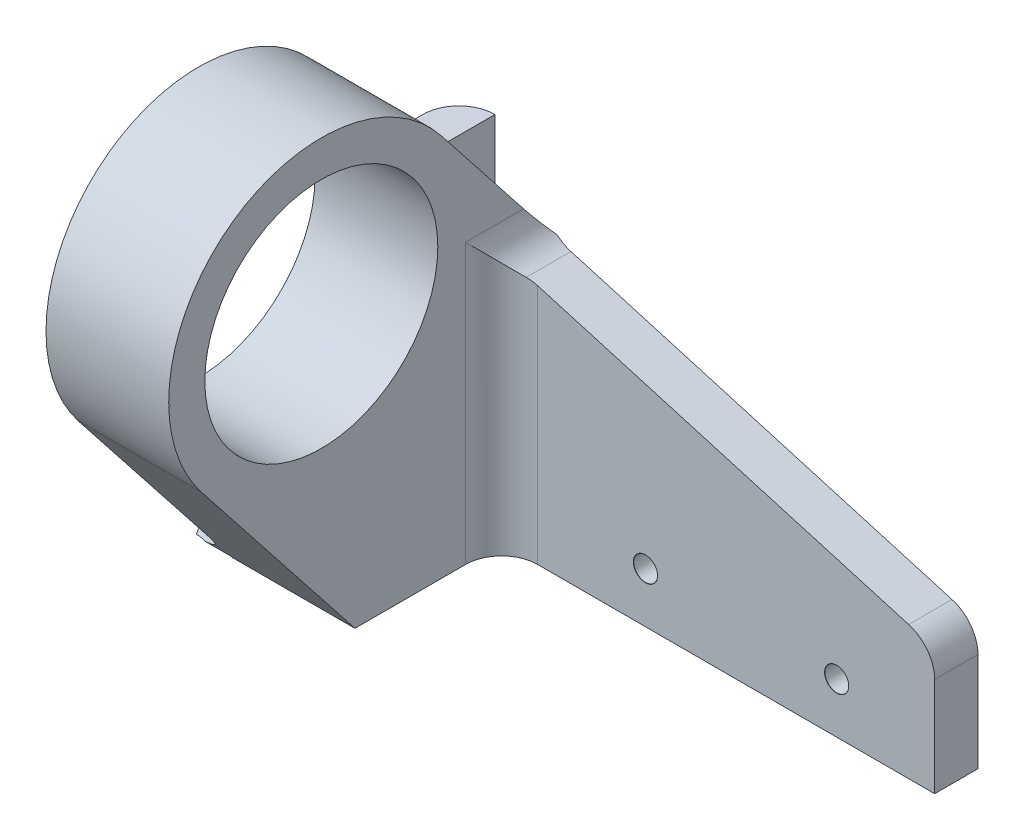
SolidWorks part; units mm, degrees
ref_plane "Front Plane" through (0, 0, 0) normal (0, 0, 1) x (1, 0, 0)
ref_plane "Top Plane" through (0, 0, 0) normal (0, 1, 0) x (1, 0, 0)
ref_plane "Right Plane" through (0, 0, 0) normal (1, 0, 0) x (0, 0, -1)
sketch "Sketch1" plane through (0, 0, 0) normal (1, 0, 0) x (0, 0, -1)
  circle A0 centre (0, 0) radius 16.14
  circle A1 centre (0, 0) radius 21.14
  dimension "D1" = 32.28
  dimension "D2" = 5
extrude "Boss-Extrude1" add sketch "Sketch1" along normal blind 17
sketch "Sketch2" plane through (0, 0, 0) normal (-1, 0, 0) x (0, 0, 1)
  line L0 (-30.9786, -40.0522) -> (-30.9786, -5.1424)
  line L1 (-30.9786, -5.1424) -> (-16.5991, 13.0908)
  line L2 (-30.9786, -40.0522) -> (-4.6638, -40.0522)
  line L4 (-4.6638, -40.0522) -> (16.5991, -13.0908)
  circle A0 centre (0, 0) radius 21.14 construction
  arc A1 (-16.5991, 13.0908) -> (16.5991, -13.0908) centre (0, 0) ccw
  dimension "D1" = 4.6638
extrude "Boss-Extrude2" add sketch "Sketch2" against normal up to surface (17 mm away) up to face at (17, 0, -21.14)
sketch "Sketch3" plane through (17, 0, 0) normal (1, 0, 0) x (0, 0, -1)
  line L0 (30.9786, -5.1424) -> (30.9786, -40.0522) construction
  line L1 (30.9786, -5.1424) -> (24.9786, -5.1424)
  line L2 (30.9786, -5.1424) -> (30.9786, -40.0522)
  line L3 (30.9786, -40.0522) -> (24.9786, -40.0522)
  line L4 (24.9786, -5.1424) -> (24.9786, -40.0522)
  line L5 (30.9786, -40.0522) -> (4.6638, -40.0522) construction
  line L6 (31.2951, -34.8407) -> (30.73, 18.1874) construction
  dimension "D1" = 6
extrude "Boss-Extrude3" add sketch "Sketch3" along normal blind 60
sketch "Sketch4" plane through (0, 0, -24.9786) normal (0, 0, 1) x (1, 0, 0)
  line L0 (17, -5.1424) -> (77, -22.5973)
  line L1 (77, -5.1424) -> (77, -40.0522) construction
  line L3 (77, -5.1424) -> (77, -22.5973)
  line L4 (77, -5.1424) -> (17, -5.1424)
  dimension "D1" = 17
extrude "Cut-Extrude1" cut sketch "Sketch4" against normal blind 30
fillet "Fillet1" radius 5 3 edges at (17, -22.5973, -24.9786) (77, -22.5973, -27.9786) (17, -5.1424, -27.9786)
sketch "Sketch5" plane through (0, 0, 0) normal (-1, 0, 0) x (0, 0, 1)
  line L0 (-36.3481, -39.7871) -> (-246.3362, -37.5493) construction
  line L1 (-30.9786, -5.0984) -> (-41.0665, -5.0984)
  line L3 (-25.5019, -39.7368) -> (-41.0665, -39.7368)
  line L4 (-41.0665, -5.0984) -> (-41.0665, -39.7368)
  line L5 (-30.9786, -5.0984) -> (-4.6638, -39.7368)
  line L6 (-30.9786, -5.1424) -> (-30.9786, -40.0522) construction
  line L7 (-4.6638, -39.7368) -> (-25.5019, -39.7368)
  dimension "D2" = 10.0879
extrude "Boss-Extrude4" add sketch "Sketch5" along normal blind 5
fillet "Fillet2" radius 5 5 edges at (-2.5, -5.0984, -41.0665) (-2.5, -39.7368, -41.0665) (0, -22.4288, -17.8127) (-2.5, -39.7368, -4.6638) (-5, -22.4176, -41.0665)
hole_wizard "Tap Drill for M4x0.7 Tap1" positions "Sketch6" profile "Sketch7" hole size "M4x0.7" standard "ANSI Metric"
sketch "Sketch6" plane through (-5, 0, 0) normal (-1, 0, 0) x (0, 0, 1)
  point P0 (-35.1563, -14.7013)
  point P2 (-35.1563, -34.1067)
sketch "Sketch7" plane through (-5, -14.7013, -35.1563) normal (0, 1, 0) x (0, 0, 1)
  line L0 (0, 0) -> (0, 5.9914)
  line L1 (0, 5.9914) -> (1.65, 5)
  line L2 (1.65, 5) -> (1.65, 0.021)
  line L3 (1.65, 0.021) -> (1.675, 0)
  line L5 (1.675, 0) -> (0, 0)
  line L6 (-1.65, 0.021) -> (-1.675, 0) construction
  line L10 (0, 5.9914) -> (-1.65, 5) construction
  line L11 (0, -6.35) -> (0, 107.95) construction
  dimension "Hole Dia." = 3.3
  dimension "Hole Depth" = 5
  dimension "Near C'Sink Dia." = 3.35
  dimension "Near C'Sink Angle" = 100
  dimension "Drill Angle" = 118
hole_wizard "Tap Drill for M4x0.7 Tap2" positions "Sketch8" profile "Sketch9" hole size "M4x0.7" standard "ANSI Metric"
sketch "Sketch8" plane through (0, 0, -24.9786) normal (0, 0, 1) x (1, 0, 0)
  point P0 (36.9326, -33.0951)
  point P2 (63.4184, -33.0951)
sketch "Sketch9" plane through (36.9326, -33.0951, -24.9786) normal (1, 0, 0) x (0, -1, 0)
  line L0 (0, 0) -> (0, 7.9914)
  line L1 (0, 7.9914) -> (1.65, 7)
  line L2 (1.65, 7) -> (1.65, 0.021)
  line L3 (1.65, 0.021) -> (1.675, 0)
  line L5 (1.675, 0) -> (0, 0)
  line L6 (-1.65, 0.021) -> (-1.675, 0) construction
  line L10 (0, 7.9914) -> (-1.65, 7) construction
  line L11 (0, -6.35) -> (0, 107.95) construction
  dimension "Hole Dia." = 3.3
  dimension "Hole Depth" = 7
  dimension "Near C'Sink Dia." = 3.35
  dimension "Near C'Sink Angle" = 100
  dimension "Drill Angle" = 118
